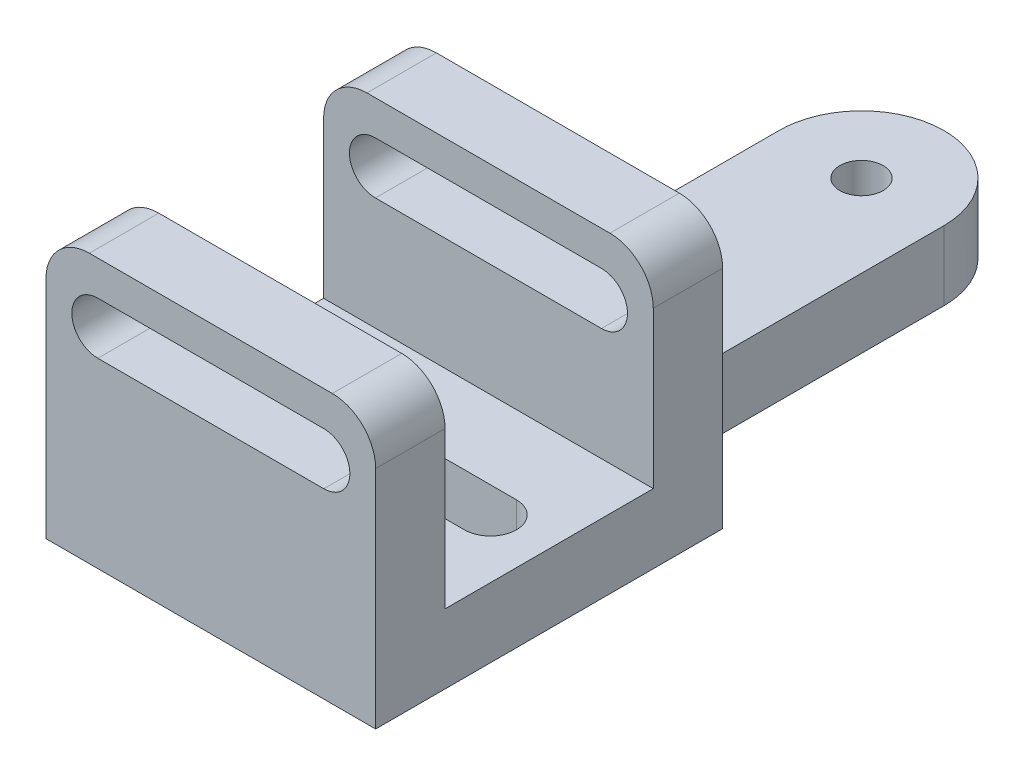
SolidWorks part; units mm, degrees
ref_plane "Piano frontale" through (0, 0, 0) normal (0, 0, 1) x (1, 0, 0)
ref_plane "Piano superiore" through (0, 0, 0) normal (0, 1, 0) x (1, 0, 0)
ref_plane "Piano destro" through (0, 0, 0) normal (1, 0, 0) x (0, 0, -1)
sketch "Schizzo2" plane through (0, 0, 0) normal (1, 0, 0) x (0, 0, -1)
  line L0 (0, 59.5033) -> (0, -49.8824) construction
  line L5 (-24, 16) -> (-24, 62)
  line L6 (-24, 62) -> (-40, 62)
  line L7 (-40, 62) -> (-40, 0)
  line L9 (-24, 16) -> (24, 16)
  line L10 (-40, 0) -> (40, 0)
  line L11 (40, 62) -> (40, 0)
  line L12 (24, 62) -> (40, 62)
  line L13 (24, 16) -> (24, 62)
  point P6 (0, 0)
  point P8 (0, 16)
  dimension "D1" = 80
  dimension "D2" = 16
  dimension "D3" = 16
  dimension "D4" = 62
extrude "Estrusione-Estrusione1" add sketch "Schizzo2" along normal mid plane 76
fillet "Raccordo1" radius 10 4 edges at (-38, 62, 32) (-38, 62, -32) (38, 62, -32) (38, 62, 32)
sketch "Schizzo3" plane through (0, 0, 0) normal (0, -1, 0) x (1, 0, 0)
  line L0 (0, 0) -> (0, -129) construction
  line L1 (38, -40) -> (-38, -40) construction
  line L2 (19, -40) -> (-19, -40)
  line L3 (-19, -40) -> (-19, -129)
  line L4 (-19, -129) -> (19, -129)
  line L5 (19, -40) -> (19, -129)
  point P9 (0, -40)
  dimension "D1" = 89
  dimension "D2" = 38
extrude "Estrusione-Estrusione2" add sketch "Schizzo3" against normal blind 16
fillet "Raccordo3" radius 19 2 edges at (19, 8, -129) (-19, 8, -129) first distance on face at (0, 8, -129)
fillet "Raccordo4" radius 14 2 edges at (-19, 8, -40) (19, 8, -40) first distance on face at (0, 26.4142, -40)
hole_wizard "Foro Ø10.0 (10)-1" positions "Schizzo3D2" profile "Schizzo4" hole size "Ø10.0" standard "ISO" end condition up to next
sketch3d "Schizzo3D2"
  line L2 (-38, 0, -40) -> (38, 0, -40)
  line L4 (0, 0, -40) -> (0, 0, -110) construction
  point P2 (0, 0, -110)
  point P16 (0, 16, -110)
  point P19 (0.0586, 16, -110.0971)
  point P20 (0.0001, 16, -110.0002)
  point P21 (0, 16, -110)
  point P22 (0, 16, -110)
  dimension "D1" = 70
sketch "Schizzo4" plane through (0, 16, -110) normal (1, 0, 0) x (0, 0, 1)
  line L0 (0, 0) -> (0, 16.001)
  line L1 (0, 16.001) -> (5, 16.001)
  line L2 (5, 16.001) -> (5, 0)
  line L5 (5, 0) -> (0, 0)
  line L11 (0, -6.35) -> (0, 107.95) construction
  dimension "Thru Hole Dia." = 10
  dimension "Thru Hole Depth" = 16.001
sketch "Schizzo5" plane through (0, 0, -40) normal (0, 0, -1) x (-1, 0, 0)
  line L0 (-26.0518, 48) -> (26.0518, 48) construction
  line L1 (-26.0518, 54) -> (26.0518, 54)
  line L2 (-26.0518, 42) -> (26.0518, 42)
  line L3 (-28, 62) -> (28, 62) construction
  arc A0 (-26.0518, 54) -> (-26.0518, 42) centre (-26.0518, 48) ccw
  arc A1 (26.0518, 42) -> (26.0518, 54) centre (26.0518, 48) ccw
  point P2 (0, 48)
  point P7 (0, 50.5165)
  point P8 (0, 49.8984)
  point P11 (0, 0)
  dimension "D1" = 12
  dimension "D2" = 14
extrude "Taglio-Estrusione1" cut sketch "Schizzo5" against normal through all
sketch "Schizzo6" plane through (0, 16, 0) normal (0, 1, 0) x (1, 0, 0)
  line L0 (-25.972, 0) -> (24.4547, 0) construction
  line L1 (-25.972, 6) -> (24.4547, 6)
  line L2 (-25.972, -6) -> (24.4547, -6)
  arc A0 (-25.972, 6) -> (-25.972, -6) centre (-25.972, 0) ccw
  arc A1 (24.4547, -6) -> (24.4547, 6) centre (24.4547, 0) ccw
  point P3 (-0.7586, 0)
  dimension "D1" = 12
extrude "Taglio-Estrusione2" cut sketch "Schizzo6" against normal up to next
